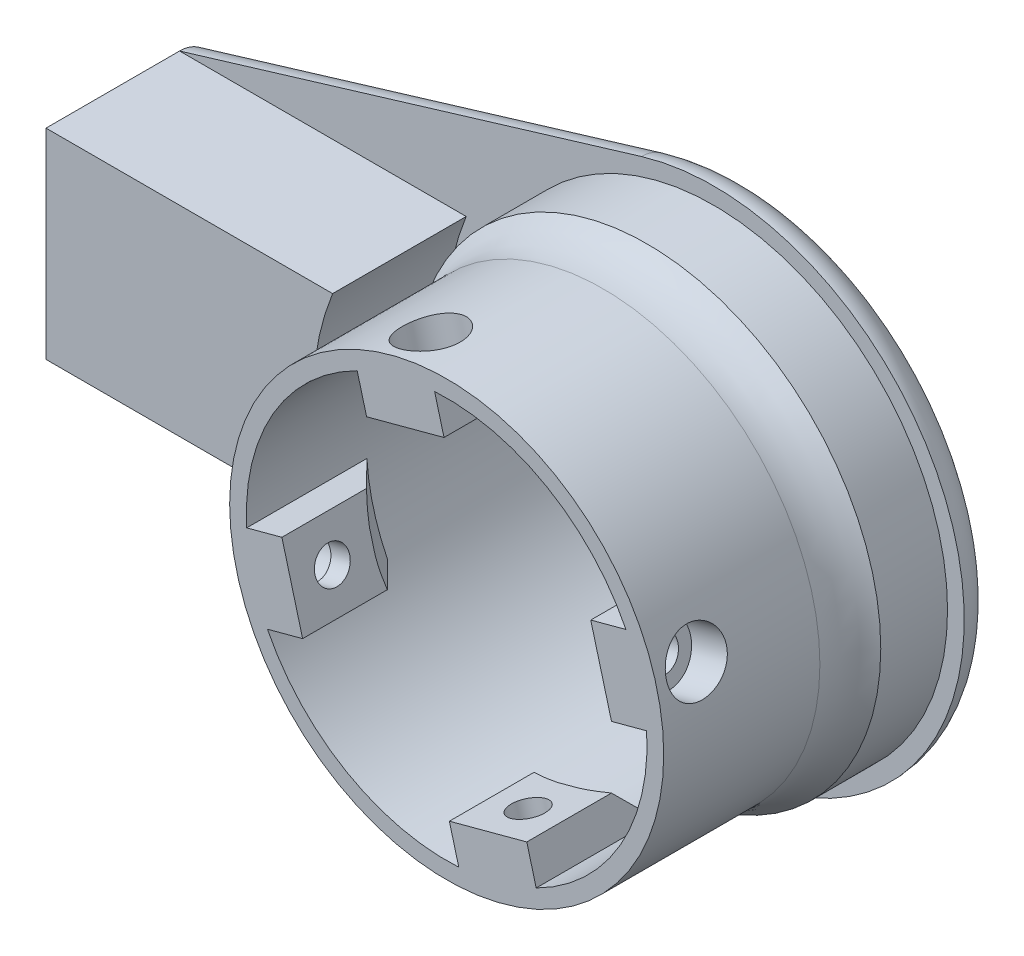
SolidWorks part; units mm, degrees
ref_plane "Plan de face" through (0, 0, 0) normal (0, 0, 1) x (1, 0, 0)
ref_plane "Plan de dessus" through (0, 0, 0) normal (0, 1, 0) x (1, 0, 0)
ref_plane "Plan de droite" through (0, 0, 0) normal (1, 0, 0) x (0, 0, -1)
sketch "Esquisse1" plane through (0, 0, 0) normal (0, 0, 1) x (1, 0, 0)
  line L0 (-1000, 0) -> (49000, 0) construction
  line L1 (-10.8475, 35.8968) -> (-80, 15)
  line L2 (-80, 15) -> (-80, -15)
  line L3 (-10.8475, -35.8968) -> (-80, -15)
  arc A0 (-10.8475, -35.8968) -> (-10.8475, 35.8968) centre (0, 0) ccw
  circle A1 centre (0, 0) radius 30
  point P9 (-80, 0)
  dimension "D1" = 75
  dimension "D4" = 60
  dimension "D2" = 15
  dimension "D3" = 80
extrude "Boss.-Extru.1" add sketch "Esquisse1" along normal blind 5
sketch "Esquisse6" plane through (0, 0, 5) normal (0, 0, 1) x (1, 0, 0)
  circle A0 centre (0, 0) radius 35
  circle A1 centre (0, 0) radius 30
  dimension "D1" = 70
  dimension "D2" = 60
extrude "Boss.-Extru.6" add sketch "Esquisse6" along normal blind 10
sketch "Esquisse7" plane through (0, 0, 15) normal (0, 0, 1) x (1, 0, 0)
  circle A0 centre (0, 0) radius 30
  circle A1 centre (0, 0) radius 32.5
  dimension "D1" = 65
extrude "Boss.-Extru.8" add sketch "Esquisse7" along normal blind 30
fillet "Congé2" radius 10 1 edges at (32.5, 0, 15)
sketch "Esquisse8" plane through (0, 0, 5) normal (0, 0, 1) x (1, 0, 0)
  line L0 (-80, 15) -> (-37.081, 15)
  line L1 (-1000, 0) -> (49000, 0) construction
  line L2 (-80, 15) -> (-80, -15)
  line L3 (-80, 15) -> (-80, -15) construction
  line L4 (-80, -15) -> (-37.081, -15)
  arc A0 (-37.081, 15) -> (-37.081, -15) centre (0, 0) ccw
  point P12 (-80, 0)
  dimension "D1" = 80
extrude "Boss.-Extru.9" add sketch "Esquisse8" along normal blind 20
sketch "Esquisse9" plane through (0, 0, 45) normal (0, 0, 1) x (1, 0, 0)
  line L7 (-1000, 0) -> (49000, 0) construction
  line L8 (0, 0) -> (-3034.415, -813.0691) construction
  line L11 (-32.4059, -2.4715) -> (-29.3001, -14.0626)
  line L13 (-32.4059, -2.4715) -> (-24.6785, -0.4009)
  line L15 (-24.6785, -0.4009) -> (-21.5727, -11.992)
  line L17 (-29.3001, -14.0626) -> (-21.5727, -11.992)
  circle A2 centre (0, 0) radius 32.5 construction
  point P22 (0, 0)
  dimension "D1" = 15
  dimension "D2" = 12
  dimension "D5" = 8
extrude "Boss.-Extru.10" add sketch "Esquisse9" against normal blind 12
chamfer "Chanfrein1" distance 6 angle 45 1 edges at (-28.9778, -7.7646, 33)
fillet "Congé3" radius 5 3 edges at (37.5, 0, 0) (-45.4237, 25.4484, 0) (-45.4237, -25.4484, 0)
sketch "Esquisse10" plane through (-23.1256, -6.1965, 0) normal (0.9659, 0.2588, 0) x (0, 0, -1)
  line L0 (-45, 32.5) -> (-45, -32.5) construction
  circle A0 centre (-39, 0) radius 4.5
  dimension "D1" = 9
  dimension "D2" = 6
extrude "Enlèv. mat.-Extru.1" cut sketch "Esquisse10" against normal up to next
sketch "Esquisse11" plane through (-23.1256, -6.1965, 0) normal (0.9659, 0.2588, 0) x (0, 0, -1)
  line L0 (-45, 32.5) -> (-45, -32.5) construction
  circle A0 centre (-39, 0) radius 2.6
  circle A1 centre (-39, 0) radius 4.5
  dimension "D2" = 5.2
  dimension "D3" = 9
  dimension "D1" = 6
extrude "Boss.-Extru.11" add sketch "Esquisse11" against normal blind 3
pattern_circular "Répétition circulaire1" count 4 every 90 about axis through (0, 0, 45) along (0, 0, 1) of "Chanfrein1", "Boss.-Extru.10", "Boss.-Extru.11", "Enlèv. mat.-Extru.1"
